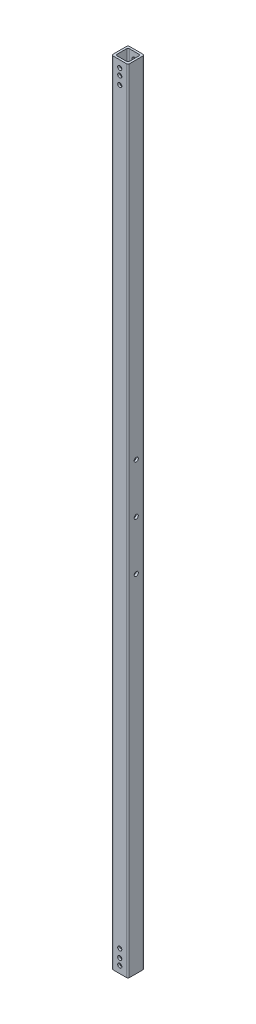
SolidWorks part; units mm, degrees
material "6061-T6 (SS)"
ref_plane "Front Plane" through (0, 0, 0) normal (0, 0, 1) x (1, 0, 0)
ref_plane "Top Plane" through (0, 0, 0) normal (0, 1, 0) x (1, 0, 0)
ref_plane "Right Plane" through (0, 0, 0) normal (1, 0, 0) x (0, 0, -1)
sketch "Sketch1" plane through (0, 0, 0) normal (0, 1, 0) x (1, 0, 0)
  line L0 (9.525, 9.525) -> (-9.525, 9.525)
  line L1 (12.7, -12.7) -> (-12.7, -12.7)
  line L2 (12.7, -12.7) -> (12.7, 12.7)
  line L3 (12.7, 12.7) -> (-12.7, 12.7)
  line L4 (-12.7, -12.7) -> (-12.7, 12.7)
  line L5 (12.7, -12.7) -> (-12.7, 12.7) construction
  line L6 (12.7, 12.7) -> (-12.7, -12.7) construction
  line L7 (-9.525, -9.525) -> (-9.525, 9.525)
  line L8 (9.525, -9.525) -> (-9.525, -9.525)
  line L9 (9.525, -9.525) -> (9.525, 9.525)
  point P0 (0, 0)
  dimension "D1" = 25.4
  dimension "D2" = 25.4
  dimension "D3" = 3.175
extrude "Boss-Extrude1" add sketch "Sketch1" along normal mid plane 1219.2
fillet "Fillet1" radius 2.1082 8 edges at (9.525, 0, -9.525) (-9.525, 0, -9.525) (-9.525, 0, 9.525) (9.525, 0, 9.525) (12.7, 0, -12.7) (-12.7, 0, -12.7) (-12.7, 0, 12.7) (12.7, 0, 12.7)
sketch "Sketch6" plane through (0, 0, -12.7) normal (0, 0, -1) x (-1, 0, 0)
  line L2 (0, 402.295) -> (0, -606.425) construction
  line L4 (0, -609.6) -> (0, 609.6) construction
  line L5 (-10.5918, -609.6) -> (10.5918, -609.6) construction
  line L6 (-10.5918, 609.6) -> (10.5918, 609.6) construction
  line L7 (0, 0) -> (10.5918, 0) construction
  line L8 (10.5918, -609.6) -> (10.5918, 609.6) construction
  circle A0 centre (0, -598.805) radius 3.175
  circle A1 centre (0, -588.645) radius 3.175
  circle A2 centre (0, -575.945) radius 3.175
  circle A3 centre (0, 598.805) radius 3.175
  circle A4 centre (0, 588.645) radius 3.175
  circle A5 centre (0, 575.945) radius 3.175
  point P5 (0, -598.805)
  point P9 (0, -588.645)
  point P10 (0, -575.945)
  dimension "D4" = 6.35
  dimension "D1" = 7.62
  dimension "D2" = 10.16
  dimension "D3" = 12.7
  dimension "D5" = 3.175
extrude "Cut-Extrude5" cut sketch "Sketch6" against normal through all
sketch "Sketch7" plane through (-12.7, 0, 0) normal (-1, 0, 0) x (0, 0, 1)
  circle A0 centre (0, 0) radius 3.175
  dimension "D1" = 6.35
extrude "Cut-Extrude6" cut sketch "Sketch7" against normal through all
sketch "Sketch8" plane through (-12.7, 0, 0) normal (-1, 0, 0) x (0, 0, 1)
  line L0 (0, 0) -> (0, -76.2) construction
  circle A0 centre (0, -76.2) radius 3.175
  dimension "D2" = 6.35
  dimension "D1" = 76.2
extrude "Cut-Extrude7" cut sketch "Sketch8" against normal through all
mirror "Mirror1" about plane through (0, 0, 0) normal (0, 1, 0) of "Cut-Extrude7"
